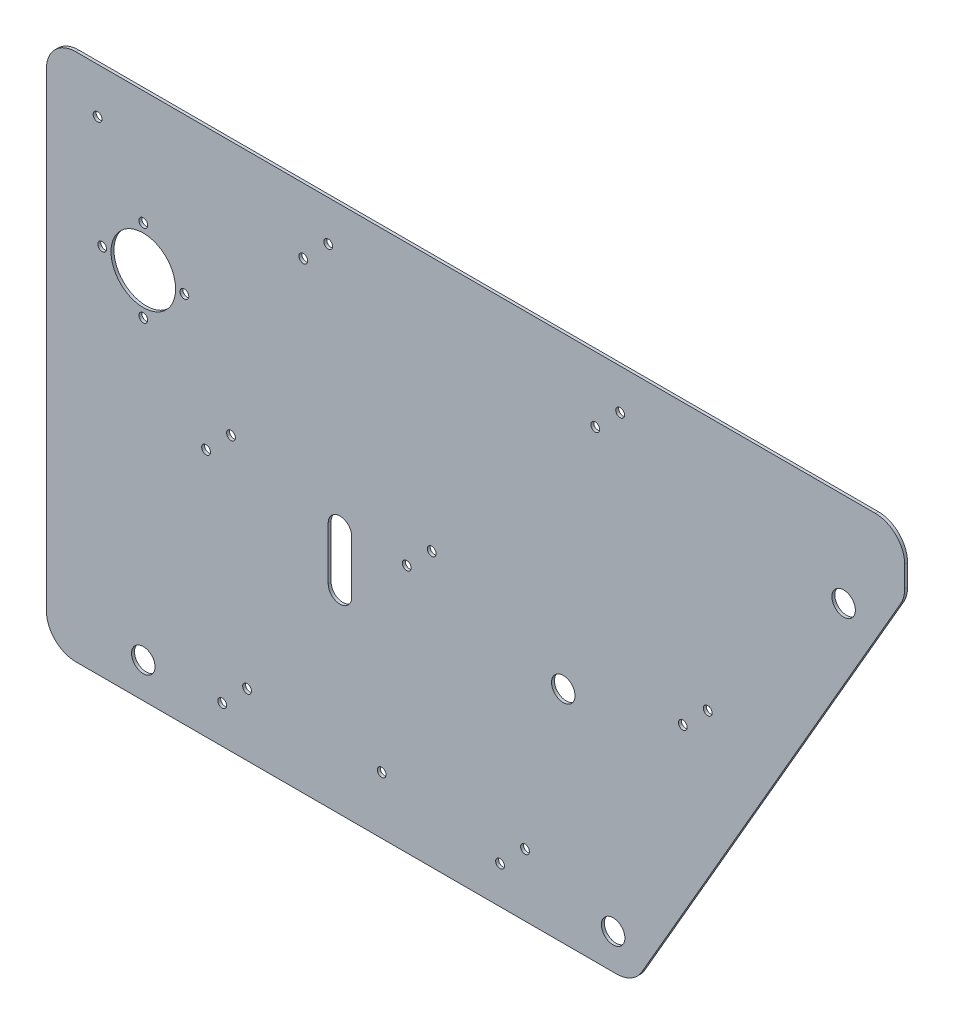
SolidWorks part; units mm, degrees
ref_plane "Front Plane" through (0, 0, 0) normal (0, 0, 1) x (1, 0, 0)
ref_plane "Top Plane" through (0, 0, 0) normal (0, 1, 0) x (1, 0, 0)
ref_plane "Right Plane" through (0, 0, 0) normal (1, 0, 0) x (0, 0, -1)
sketch "Sketch1" plane through (0, 0, 0) normal (0, 0, 1) x (1, 0, 0)
  line L0 (100, 80) -> (192.376, 80)
  line L1 (-100, -80) -> (100, -80)
  line L2 (-100, -80) -> (-100, 80)
  line L3 (-100, 80) -> (100, 80)
  line L4 (100, -80) -> (100, 80)
  line L5 (-100, -80) -> (100, 80) construction
  line L6 (-100, 80) -> (100, -80) construction
  line L7 (192.376, 80) -> (100, -80)
  line L8 (100, 80) -> (100, -80)
  line L10 (-100, 80) -> (192.376, 80)
  line L11 (-100, 80) -> (-100, 100)
  line L12 (-100, 100) -> (192.376, 100)
  line L13 (192.376, 80) -> (192.376, 100)
  point P0 (0, 0)
  dimension "D1" = 160
  dimension "D2" = 200
  dimension "D3" = 30
  dimension "D4" = 20
extrude "Boss-Extrude1" add sketch "Sketch1" along normal blind 1 contours L1 L4 L3 L2 | L7 L0 L4 | L11 L10 L13 L12 region at (0, 0, 0) region at (130.792, 26.6667, 0)
fillet "Fillet1" radius 10 5 edges at (100, -80, 0.5) (-100, -80, 0.5) (192.376, 100, 0.5) (192.376, 80, 0.5) (-100, 100, 0.5)
sketch "Sketch2" plane through (0, 0, 1) normal (0, 0, 1) x (1, 0, 0)
  line L0 (-90, -80) -> (94.2265, -80) construction
  line L1 (191.0363, 77.6795) -> (102.8868, -75) construction
  line L3 (-100, -70) -> (-100, 90) construction
  line L4 (0, -14) -> (0, 4) construction
  line L5 (-4, -14) -> (-4, 4)
  line L6 (4, -14) -> (4, 4)
  line L7 (-90, 100) -> (182.376, 100) construction
  line L8 (0, -0.55) -> (0, 0.55) construction
  circle A0 centre (93.0718, -68) radius 4
  circle A1 centre (171.5914, 68) radius 4
  circle A2 centre (-67, 47) radius 11
  circle A3 centre (-67, -68) radius 4
  circle A4 centre (-53, 47) radius 1.5
  circle A5 centre (-67, 61) radius 1.5
  circle A6 centre (-81, 47) radius 1.5
  circle A7 centre (-67, 33) radius 1.5
  arc A8 (-4, -14) -> (4, -14) centre (0, -14) ccw
  arc A9 (4, 4) -> (-4, 4) centre (0, 4) ccw
  circle A10 centre (76.0815, -5) radius 4
  circle A11 centre (54.5495, -67.2426) radius 1.5
  circle A12 centre (63.0348, -58.7574) radius 1.5
  circle A13 centre (14.2259, -60.5) radius 1.5
  circle A14 centre (-40.1271, -67.2426) radius 1.5
  circle A15 centre (-31.6419, -58.7574) radius 1.5
  circle A16 centre (-82.5763, 84.5) radius 1.5
  circle A17 centre (-12.4828, 77.7574) radius 1.5
  circle A18 centre (-3.9975, 86.2426) radius 1.5
  circle A19 centre (86.9654, 77.7574) radius 1.5
  circle A20 centre (95.4507, 86.2426) radius 1.5
  circle A21 centre (22.7626, 4.7574) radius 1.5
  circle A22 centre (31.2479, 13.2426) radius 1.5
  circle A23 centre (-45.6014, 4.7574) radius 1.5
  circle A24 centre (-37.1161, 13.2426) radius 1.5
  circle A25 centre (116.8113, 4.7574) radius 1.5
  circle A26 centre (125.2966, 13.2426) radius 1.5
  point P24 (0, -5)
  dimension "D3" = 8
  dimension "D4" = 8
  dimension "D9" = 22
  dimension "D10" = 8
  dimension "D12" = 3
  dimension "D13" = 3
  dimension "D14" = 3
  dimension "D15" = 3
  dimension "D16" = 14
  dimension "D20" = 4
  dimension "D22" = 8
  dimension "D25" = 3
  dimension "D26" = 3
  dimension "D1" = 12
  dimension "D2" = 12
  dimension "D5" = 32
  dimension "D6" = 12
  dimension "D7" = 53
  dimension "D8" = 33
  dimension "D11" = 12
  dimension "D17" = 14
  dimension "D18" = 14
  dimension "D19" = 14
  dimension "D21" = 18
  dimension "D23" = 105
  dimension "D24" = 105
extrude "Cut-Extrude1" cut sketch "Sketch2" against normal blind 3
